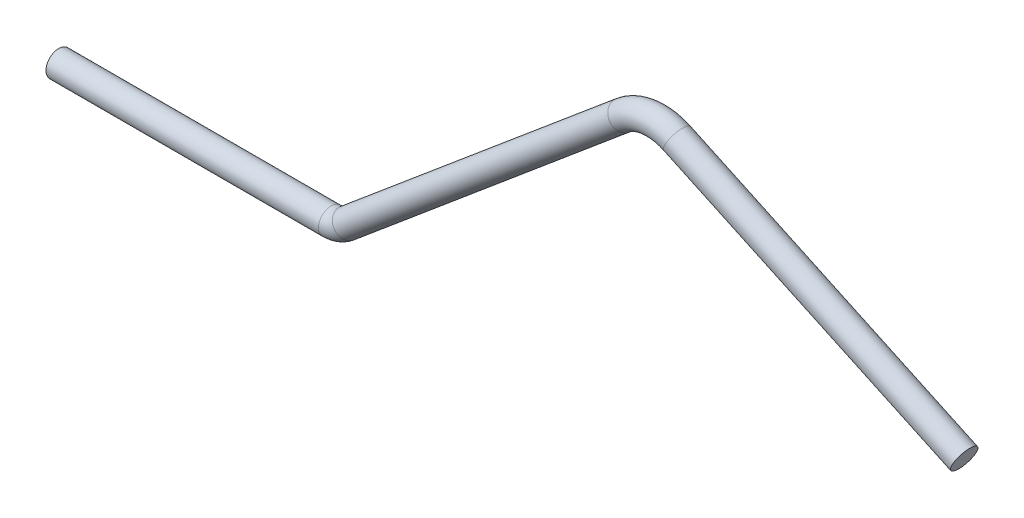
SolidWorks part; units mm, degrees
ref_plane "Front" through (0, 0, 0) normal (0, 0, 1) x (1, 0, 0)
ref_plane "Top" through (0, 0, 0) normal (0, 1, 0) x (1, 0, 0)
ref_plane "Right" through (0, 0, 0) normal (1, 0, 0) x (0, 0, -1)
sketch "Esquisse1" plane through (0, 0, 0) normal (0, 0, 1) x (1, 0, 0)
  line L0 (0, 0) -> (12.8162, 0)
  line L1 (16.6729, 1.4037) -> (59.9405, 37.7095)
  line L2 (66.3329, 38.5511) -> (111.4365, 17.519)
  line L3 (0, 0) -> (26.6873, -41.0949) construction
  line L4 (0, 0) -> (91.4151, 59.3657) construction
  line L5 (26.6873, -41.0949) -> (118.1024, 18.2708) construction
  line L6 (91.4151, 59.3657) -> (118.1024, 18.2708) construction
  arc A0 (66.3329, 38.5511) -> (59.9405, 37.7095) centre (63.7972, 33.1133) ccw
  arc A1 (16.6729, 1.4037) -> (12.8162, 0) centre (12.8162, 6) cw
  point P6 (62.8686, 40.1665)
  point P14 (15, 0)
  dimension "D5" = 15
  dimension "D7" = 6
  dimension "D1" = 57
  dimension "D2" = 3
  dimension "D3" = 49
  dimension "D4" = 109
  dimension "D6" = 103
  dimension "D8" = 25
  dimension "D9" = 140
  dimension "D10" = 115
sketch "Esquisse2" plane through (0, 0, 0) normal (1, 0, 0) x (0, 0, -1)
  line L1 (-1.25, 0.8) -> (1.25, 0.8) construction
  line L2 (-1.25, 0.8) -> (-1.25, 0) construction
  line L3 (-1.25, 0) -> (1.25, 0) construction
  line L4 (1.25, 0.8) -> (1.25, 0) construction
  circle A0 centre (0, 2) radius 2
  point P7 (0, 0)
  dimension "D1" = 4
  dimension "D2" = 2.5
  dimension "D3" = 0.8
sweep "Balayage1" add profiles "Esquisse2" path "Esquisse1"
extrude "Boss.-Extru.1" add sketch "Esquisse2<2>" against normal blind 30
sketch "Esquisse2<2>" plane through (0, 0, 0) normal (1, 0, 0) x (0, 0, -1) same geometry as "Esquisse2"
